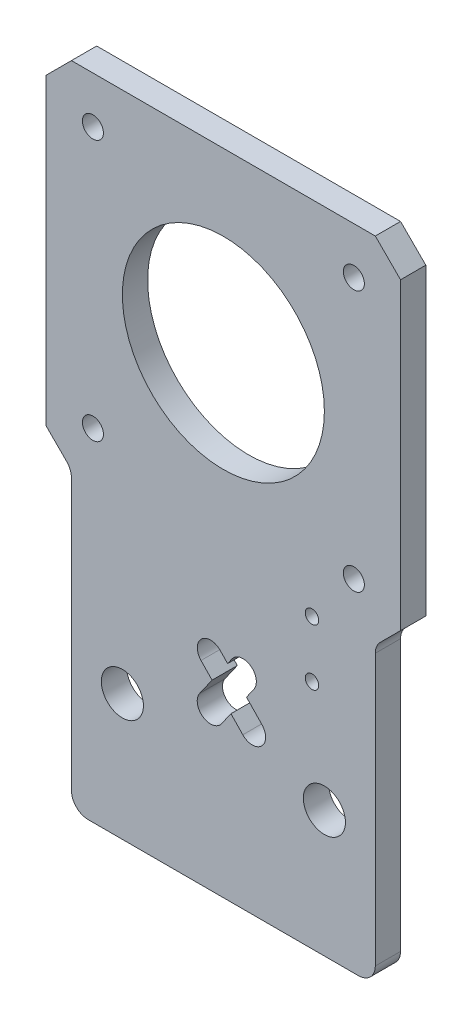
SolidWorks part; units mm, degrees
ref_plane "Plano frontal" through (0, 0, 0) normal (0, 0, 1) x (1, 0, 0)
ref_plane "Plano superior" through (0, 0, 0) normal (0, 1, 0) x (1, 0, 0)
ref_plane "Plano direito" through (0, 0, 0) normal (1, 0, 0) x (0, 0, -1)
sketch "Sketch1" plane through (0, 0, 0) normal (0, 0, 1) x (1, 0, 0)
  line L0 (149.1978, -56.055) -> (-642.8022, -56.055) construction
  line L2 (18.05, -56.055) -> (18.05, -21.05)
  line L4 (-18.05, -56.055) -> (-18.05, -21.05)
  line L5 (18.05, -56.055) -> (-18.05, -56.055)
  line L16 (-21.05, -18.05) -> (-18.05, -21.05)
  line L18 (18.05, -21.05) -> (21.05, -18.05)
  line L19 (21.05, -18.05) -> (21.05, 18.05)
  line L20 (21.05, 18.05) -> (18.05, 21.05)
  line L21 (18.05, 21.05) -> (-18.05, 21.05)
  line L22 (-18.05, 21.05) -> (-21.05, 18.05)
  line L23 (-21.05, 18.05) -> (-21.05, -18.05)
  circle A3 centre (0, 0) radius 12
  dimension "D2" = 36.1
  dimension "D3" = 4.2426
extrude "Boss-Extrude1" add sketch "Sketch1" along normal blind 3
hole_wizard "Tap Drill for M3 Tap1" positions "Sketch3" profile "Sketch2" hole size "M3" standard "ISO"
sketch "Sketch3" plane through (0, 0, 3) normal (0, 0, 1) x (1, 0, 0)
  point P0 (-15.5, 15.5)
  point P3 (15.5, 15.5)
  point P6 (-15.5, -15.5)
  point P9 (15.5, -15.5)
sketch "Sketch2" plane through (-15.5, 15.5, 3) normal (1, 0, 0) x (0, -1, 0)
  line L0 (0, 0) -> (0, 5.7511)
  line L1 (0, 5.7511) -> (1.25, 5)
  line L2 (1.25, 5) -> (1.25, 0)
  line L5 (1.25, 0) -> (0, 0)
  line L10 (0, 5.7511) -> (-1.25, 5) construction
  line L11 (0, -6.35) -> (0, 107.95) construction
  dimension "Hole Dia." = 2.5
  dimension "Hole Depth" = 5
  dimension "Drill Angle" = 118
hole_wizard "Tap Drill for M4 Tap1" positions "Sketch5" profile "Sketch4" hole size "M6" standard "ISO"
sketch "Sketch5" plane through (0, 0, 3) normal (0, 0, 1) x (1, 0, 0)
  line L1 (0, -56.055) -> (0, -21.05) construction
  line L2 (-18.05, -56.055) -> (18.05, -56.055) construction
  line L3 (149.1978, -41.055) -> (-642.8022, -41.055) construction
  point P40 (-12, -41.055)
  point P45 (12, -41.055)
  dimension "D1" = 12
sketch "Sketch4" plane through (12, -41.055, 3) normal (1, 0, 0) x (0, -1, 0)
  line L0 (0, 0) -> (0, 6.5022)
  line L1 (0, 6.5022) -> (2.5, 5)
  line L2 (2.5, 5) -> (2.5, 0)
  line L5 (2.5, 0) -> (0, 0)
  line L10 (0, 6.5022) -> (-2.5, 5) construction
  line L11 (0, -6.35) -> (0, 107.95) construction
  dimension "Hole Dia." = 5
  dimension "Hole Depth" = 5
  dimension "Drill Angle" = 118
fillet "Fillet1" radius 2 4 edges at (18.05, -21.05, 1.5) (18.05, -56.055, 1.5) (-18.05, -56.055, 1.5) (-18.05, -21.05, 1.5)
hole_wizard "Tap Drill for M2 Tap1" positions "Sketch7" profile "Sketch6" hole size "M2" standard "ISO"
sketch "Sketch7" plane through (0, 0, 3) normal (0, 0, 1) x (1, 0, 0)
  point P0 (10.5295, -21.8613)
  point P3 (10.5295, -28.5613)
sketch "Sketch6" plane through (10.5295, -21.8613, 3) normal (1, 0, 0) x (0, -1, 0)
  line L0 (0, 0) -> (0, 5.4807)
  line L1 (0, 5.4807) -> (0.8, 5)
  line L2 (0.8, 5) -> (0.8, 0)
  line L5 (0.8, 0) -> (0, 0)
  line L10 (0, 5.4807) -> (-0.8, 5) construction
  line L11 (0, -6.35) -> (0, 107.95) construction
  dimension "Hole Dia." = 1.6
  dimension "Hole Depth" = 5
  dimension "Drill Angle" = 118
sketch "Sketch8" plane through (0, 0, 0) normal (0, 0, 1) x (1, 0, 0)
  line L0 (9.1176, -56.055) -> (-8.1087, -56.055) construction
  line L1 (0.5044, -56.055) -> (0.5044, -38.2118) construction
  line L2 (0.8999, -36.6716) -> (-0.2213, -38.2661)
  line L3 (1.0288, -30.9682) -> (0.5043, -31.7142)
  line L4 (-2.6554, -32.9727) -> (-1.3417, -34.3396)
  line L7 (3.6261, -32.7944) -> (2.7458, -34.0463)
  line L11 (0.5044, -34.343) -> (0.5044, -20.8461) construction
  line L12 (0.8999, -36.6716) -> (2.3092, -38.1379)
  line L13 (4.5803, -35.9549) -> (2.7458, -34.0463)
  line L14 (0.5043, -31.7142) -> (-0.3843, -30.7898)
  line L15 (-1.3417, -34.3396) -> (-2.8185, -36.4399)
  arc A0 (3.6261, -32.7944) -> (1.0288, -30.9682) centre (2.3275, -31.8813) ccw
  arc A4 (-2.8185, -36.4399) -> (-0.2213, -38.2661) centre (-1.5199, -37.353) ccw
  arc A5 (-0.3843, -30.7898) -> (-2.6554, -32.9727) centre (-1.5199, -31.8813) ccw
  arc A6 (2.3092, -38.1379) -> (4.5803, -35.9549) centre (3.4448, -37.0464) ccw
  point P20 (0.4038, -34.6171)
  point P29 (-0.4429, -32.9927)
  point P30 (0.9624, -34.4638)
extrude "Cut-Extrude1" cut sketch "Sketch8" along normal blind 10 contours L2 A4 L15 L4 A5 L14 L3 A0 L7 L13 A6 L12
